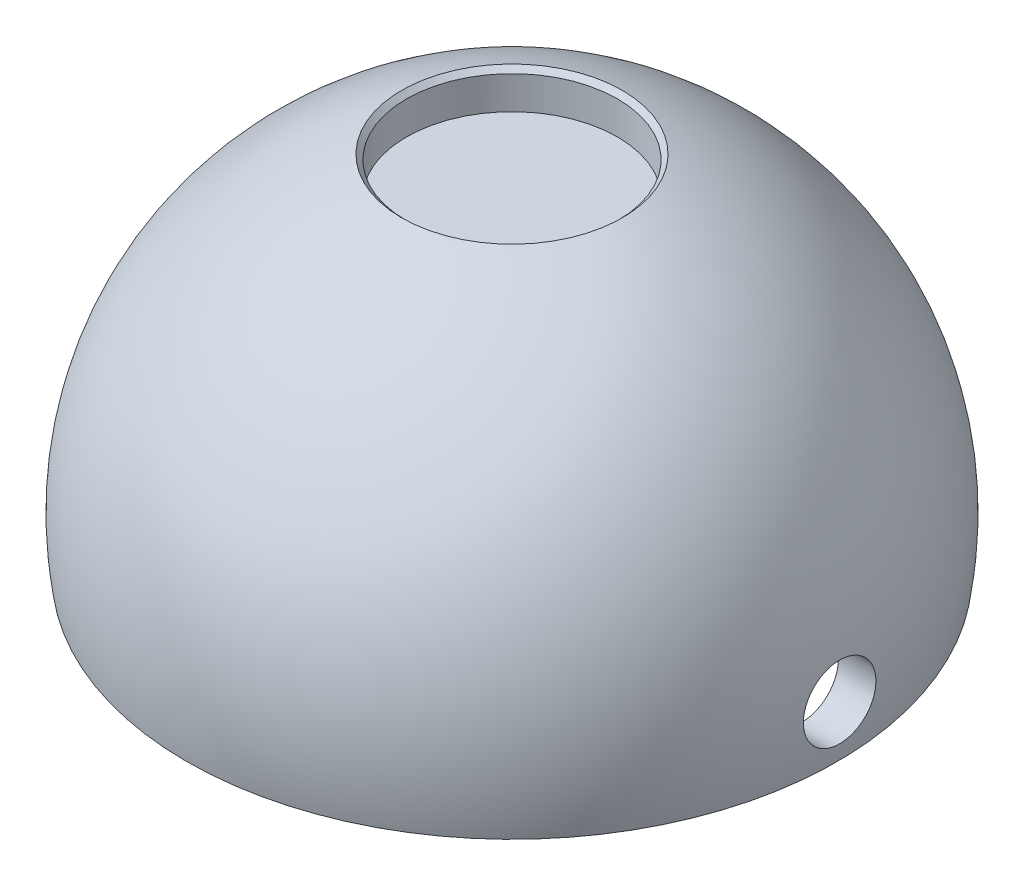
SolidWorks part; units mm, degrees
ref_plane "Front Plane" through (0, 0, 0) normal (0, 0, 1) x (1, 0, 0)
ref_plane "Top Plane" through (0, 0, 0) normal (0, 1, 0) x (1, 0, 0)
ref_plane "Right Plane" through (0, 0, 0) normal (1, 0, 0) x (0, 0, -1)
sketch "Sketch2" plane through (0, 0, 0) normal (0, 0, 1) x (1, 0, 0)
  line L0 (0, 19.1854) -> (0, 20.6854)
  line L1 (0, 20.6854) -> (8, 20.6854)
  line L2 (8, 20.6854) -> (8, 23.6854)
  line L3 (0, 19.1854) -> (14.4417, 19.1854)
  line L5 (23.6779, -4) -> (24.6779, -4)
  line L6 (0, 0) -> (0, 11.6107) construction
  arc A0 (8, 23.6854) -> (24.6779, -4) centre (0, 0) cw
  arc A1 (14.4417, 19.1854) -> (23.6779, -4) centre (0, 0) cw
  dimension "D4" = 25
  dimension "D1" = 1.5
  dimension "D2" = 16
  dimension "D3" = 3
  dimension "D5" = 4
  dimension "D6" = 1
revolve "Revolve1" add sketch "Sketch2" angle 360 about L6
sketch "Sketch4" plane through (0, 0, 0) normal (1, 0, 0) x (0, 0, -1)
  line L0 (-23.6779, -4) -> (23.6779, -4) construction
  line L1 (-5, 11) -> (5, 11)
  line L2 (-5, 11) -> (-5, -4)
  line L3 (-5, -4) -> (5, -4)
  line L4 (5, 11) -> (5, -4)
  point P6 (0, -4)
  dimension "D1" = 10
  dimension "D2" = 15
extrude "Boss-Extrude1" add sketch "Sketch4" along normal up to next from offset 22
sketch "Sketch5" plane through (22, 0, 0) normal (-1, 0, 0) x (0, 0, 1)
  circle A0 centre (0, 0) radius 2.75
  dimension "D1" = 5.5
extrude "Cut-Extrude1" cut sketch "Sketch5" against normal through all
chamfer "Chamfer1" distance 1 angle 45 2 edges at (22, 2.1123, 5) (22, 2.1123, -5)
mirror "Mirror1" about plane through (0, 0, 0) normal (1, 0, 0) of "Cut-Extrude1", "Boss-Extrude1", "Chamfer1"
chamfer "Chamfer2" distance 0.5 angle 45 1 edges at (0, 23.6854, -8) first distance on face at (0, 20.6854, -8)
ref_plane "Plane1" through (5.5, 0, 0) normal (1, 0, 0) x (0, 0, -1)
sketch "Sketch7" plane through (5.5, 0, 0) normal (1, 0, 0) x (0, 0, -1)
  line L0 (-23.6779, -4) -> (-9, -4)
  line L1 (-9, -4) -> (-9, 4)
  line L2 (-9, 4) -> (-23.6779, 4)
  arc A0 (-14.4417, 19.1854) -> (-23.6779, -4) centre (0, 0) ccw construction
  arc A1 (-23.6779, 4) -> (-23.6779, -4) centre (0, 0) ccw
  circle A2 centre (-13, 0) radius 1.6
  dimension "D1" = 3.2
  dimension "D2" = 4
  dimension "D3" = 13
  dimension "D4" = 8
  dimension "D5" = 4
extrude "Boss-Extrude2" add sketch "Sketch7" along normal up to next
sketch "Sketch8" plane through (5.5, 0, 0) normal (-1, 0, 0) x (0, 0, 1)
  circle A0 centre (13, 0) radius 1.75
  dimension "D1" = 3.5
extrude "Cut-Extrude2" cut sketch "Sketch8" along normal through all
fillet "Fillet1" radius 4 2 edges at (13.7004, 4, 9) (13.7004, -4, 9)
sketch "Sketch9" plane through (5.5, 0, 0) normal (-1, 0, 0) x (0, 0, 1)
  circle A0 centre (13, 0) radius 4
  circle A1 centre (13, 0) radius 1.6 construction
  circle A2 centre (13, 0) radius 1.6
  arc A3 (13, 4) -> (9, 0) centre (13, 0) ccw construction
extrude "Boss-Extrude3" add sketch "Sketch9" along normal blind 1.5
chamfer "Chamfer5" distance 1.5 angle 45 1 edges at (4, 0, 17)
ref_plane "Plane2" through (11, 0, 0) normal (-1, 0, 0) x (0, 0, 1)
sketch "Sketch10" plane through (11, 0, 0) normal (-1, 0, 0) x (0, 0, 1)
  line L1 (9, 3) -> (17, 3)
  line L2 (9, 3) -> (9, -3)
  line L3 (9, -3) -> (17, -3)
  line L4 (17, 3) -> (17, -3)
  point P4 (9, 0)
  dimension "D1" = 6
  dimension "D2" = 4
extrude "Cut-Extrude3" cut sketch "Sketch10" along normal blind 3
sketch "Sketch11" plane through (11, 0, 0) normal (-1, 0, 0) x (0, 0, 1)
  line L0 (23.0303, -4) -> (13, -4) construction
  line L1 (9, 4) -> (11, 4)
  line L2 (9, 4) -> (9, -4)
  line L3 (9, -4) -> (11, -4)
  line L4 (11, 4) -> (11, -4)
  point P4 (9, 0)
  dimension "D1" = 2
extrude "Cut-Extrude4" cut sketch "Sketch11" along normal up to surface (3 mm away) up to face at (8, 0, 12.6125)
chamfer "Chamfer6" distance 1 angle 45 2 edges at (5.5, 4, 18.0151) (5.5, -4, 18.0151)
